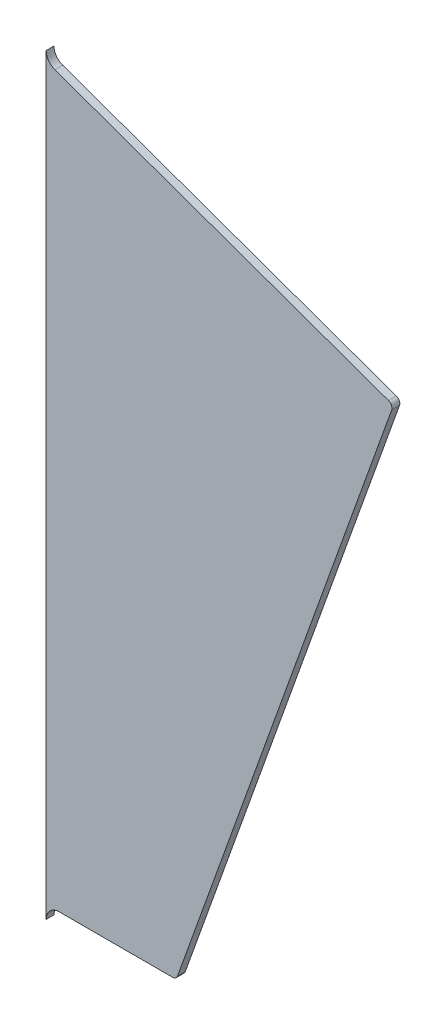
SolidWorks part; units mm, degrees
ref_plane "Спереди" through (0, 0, 0) normal (0, 0, 1) x (1, 0, 0)
ref_plane "Сверху" through (0, 0, 0) normal (0, 1, 0) x (1, 0, 0)
ref_plane "Справа" through (0, 0, 0) normal (1, 0, 0) x (0, 0, -1)
sketch "Эскиз1" plane through (0, 0, 0) normal (0, 0, 1) x (1, 0, 0)
  line L0 (67.1521, -21.9537) -> (3.1562, 0.993) construction
  line L1 (26.678, -137.7944) -> (67.7559, -23.2325) construction
  line L2 (4, -138.4569) -> (25.7367, -138.4569) construction
  line L3 (4, -138.4569) -> (25.7367, -138.4569)
  line L4 (26.678, -137.7944) -> (67.7559, -23.2325)
  line L5 (67.1521, -21.9537) -> (3.1562, 0.993)
  line L6 (1.5, -140.9569) -> (1.5, 3.3463)
  arc A0 (1.5, 3.3463) -> (3.1562, 0.993) centre (4, 3.3463) ccw construction
  arc A1 (67.7559, -23.2325) -> (67.1521, -21.9537) centre (66.8145, -22.895) ccw construction
  arc A2 (25.7367, -138.4569) -> (26.678, -137.7944) centre (25.7367, -137.4569) ccw construction
  arc A3 (4, -138.4569) -> (1.5, -140.9569) centre (4, -140.9569) ccw construction
  arc A4 (4, -138.4569) -> (1.5, -140.9569) centre (4, -140.9569) ccw
  arc A5 (1.5, 3.3463) -> (3.1562, 0.993) centre (4, 3.3463) ccw
  arc A6 (25.7367, -138.4569) -> (26.678, -137.7944) centre (25.7367, -137.4569) ccw
  arc A7 (67.7559, -23.2325) -> (67.1521, -21.9537) centre (66.8145, -22.895) ccw
base flange "Базовая кромка1" sketch "Эскиз1" thickness 1.5 reverse thickness direction no parameters "D1"=1
sketch "Сгиб-Линии1" plane through (0, 0, 0) normal (0, 1, 0) x (1, 0, 0)
sketch "Граничная рамка1" plane through (0, 0, 0) normal (0, 1, 0) x (1, 0, 0)
sheet metal parameters "Листовой металл3" thickness 1.5 parameters "D1"=1
flat pattern "Развертка3" [suppressed]
sketch "Сгиб-Линии2" plane through (0, 0, 0) normal (0, 1, 0) x (1, 0, 0)
sketch "Граничная рамка2" [suppressed] plane through (0, 0, 0) normal (0, 1, 0) x (1, 0, 0)
